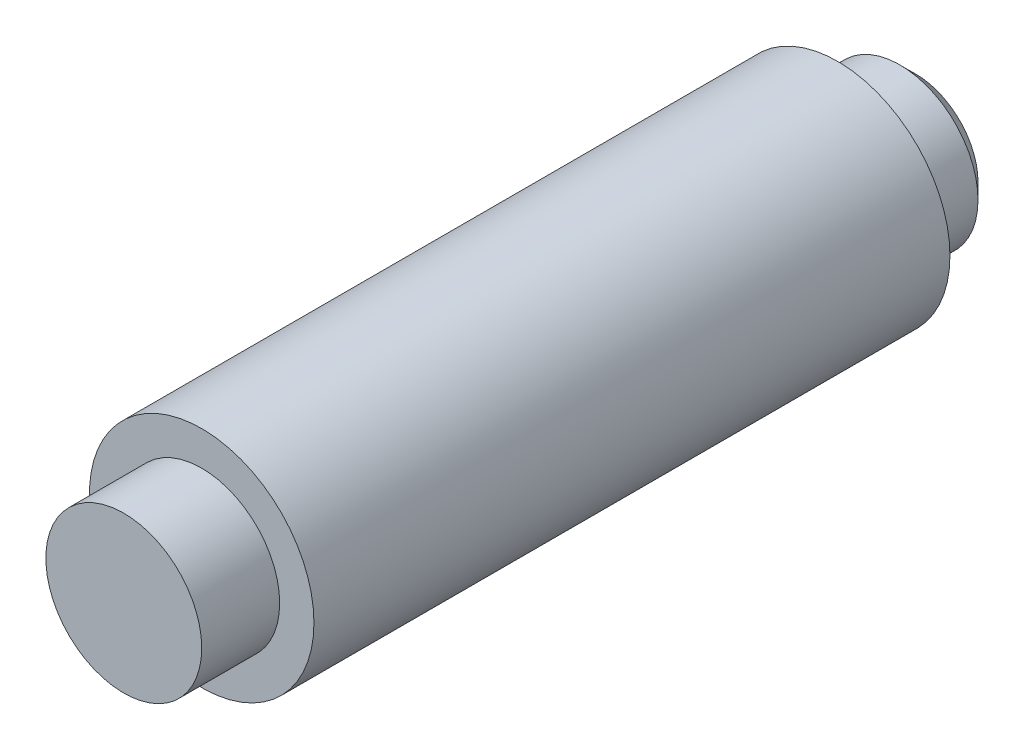
SolidWorks part; units mm, degrees
ref_plane "Front Plane" through (0, 0, 0) normal (0, 0, 1) x (1, 0, 0)
ref_plane "Top Plane" through (0, 0, 0) normal (0, 1, 0) x (1, 0, 0)
ref_plane "Right Plane" through (0, 0, 0) normal (1, 0, 0) x (0, 0, -1)
sketch "Sketch2" plane through (0, 0, 0) normal (0, 0, 1) x (1, 0, 0)
  circle A0 centre (0, 0) radius 1.25
  dimension "D1" = 2.5
sketch "Sketch3" plane through (0, 0, 0) normal (0, 0, 1) x (1, 0, 0)
  line L5 (-3.6, 3.6) -> (3.6, 3.6) construction
  line L6 (-3.6, 3.6) -> (-3.6, -3.6) construction
  line L7 (-3.6, -3.6) -> (3.6, -3.6) construction
  line L8 (3.6, 3.6) -> (3.6, -3.6) construction
  circle A0 centre (0, 0) radius 3.6
  point P4 (0, 3.6)
  point P6 (-3.6, 0)
  dimension "D1" = 7.2
extrude "Boss-Extrude1" add sketch "Sketch3" along normal blind 20.4
sketch "Sketch4" plane through (0, 0, 0) normal (0, 0, 1) x (1, 0, 0)
  circle A0 centre (0, 0) radius 2.5
  dimension "D1" = 5
extrude "Boss-Extrude2" add sketch "Sketch4" against normal blind 2.5
sketch "Sketch5" plane through (0, 0, 20.4) normal (0, 0, 1) x (1, 0, 0)
  circle A0 centre (0, 0) radius 2.5
  dimension "D1" = 5
extrude "Boss-Extrude3" add sketch "Sketch5" along normal blind 2.5
chamfer "Chamfer1" distance 0.5 angle 45 1 edges at (2.5, 0, -2.5)
equation "\"length\"=20.4"
equation "\"D1@Boss-Extrude1\"=\"length\""
